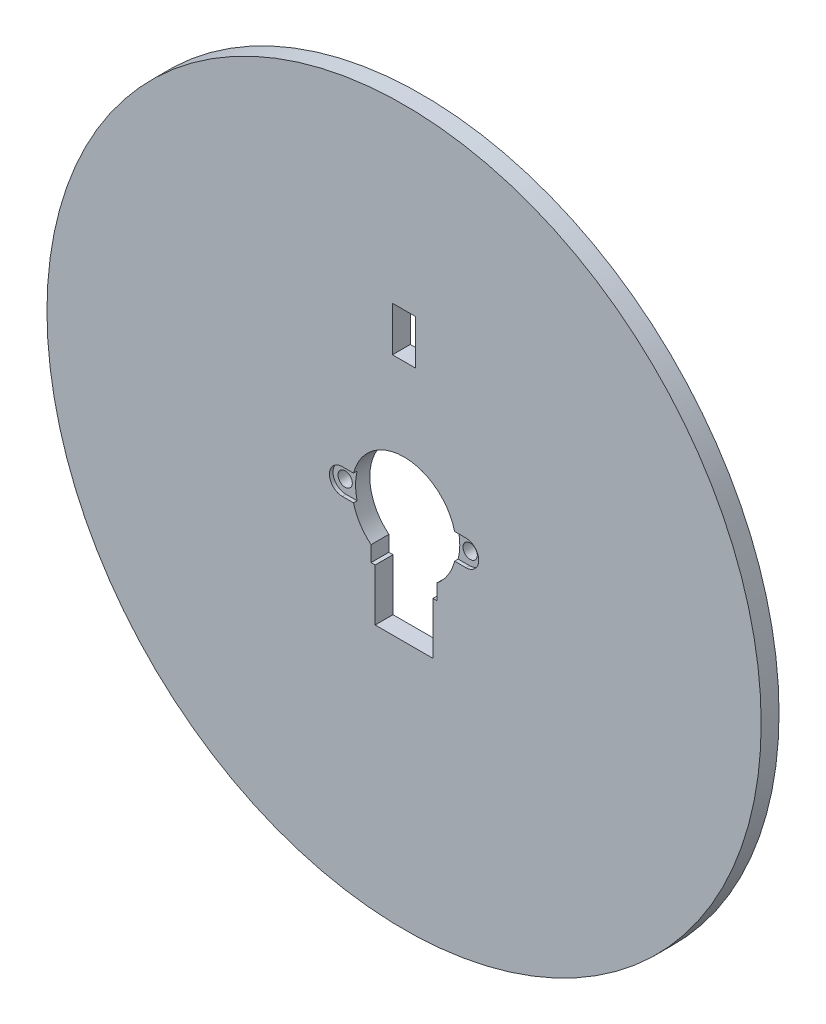
SolidWorks part; units mm, degrees
ref_plane "Front Plane" through (0, 0, 0) normal (0, 0, 1) x (1, 0, 0)
ref_plane "Top Plane" through (0, 0, 0) normal (0, 1, 0) x (1, 0, 0)
ref_plane "Right Plane" through (0, 0, 0) normal (1, 0, 0) x (0, 0, -1)
sketch "Sketch1" plane through (0, 0, 0) normal (0, 0, 1) x (1, 0, 0)
  line L0 (-121.4648, 0) -> (89.658, 0) construction
  line L1 (0, 59.7877) -> (0, -65.1952) construction
  line L2 (-14.1492, 3.6) -> (-17.3, 3.6)
  line L3 (-14.1492, -3.6) -> (-17.3, -3.6)
  line L4 (-9.25, -11.2959) -> (-9.25, -15.647)
  line L5 (14.1492, 3.6) -> (17.3, 3.6)
  line L14 (8.1, -15.647) -> (8.1, -30.2)
  line L15 (14.1492, -3.6) -> (17.3, -3.6)
  line L16 (-8.1, -30.2) -> (8.1, -30.2)
  line L24 (9.25, -11.2959) -> (9.25, -15.647)
  line L25 (8.1, -15.647) -> (9.25, -15.647)
  line L26 (-8.1, -15.647) -> (-9.25, -15.647)
  line L27 (-8.1, -15.647) -> (-8.1, -30.2)
  line L28 (-3.25, 44) -> (3.25, 44) construction
  line L29 (-3.25, 50.25) -> (3.25, 50.25)
  line L30 (-3.25, 50.25) -> (-3.25, 37.75)
  line L31 (-3.25, 37.75) -> (3.25, 37.75)
  line L32 (3.25, 50.25) -> (3.25, 37.75)
  circle A0 centre (0, 0) radius 100
  arc A2 (9.25, -11.2959) -> (-9.25, -11.2959) centre (0, 0) ccw
  arc A3 (17.3, -3.6) -> (17.3, 3.6) centre (17.3, 0) ccw
  arc A4 (-17.3, -3.6) -> (-17.3, 3.6) centre (-17.3, 0) cw
  circle A6 centre (17.5, 0) radius 2
  circle A7 centre (-17.5, 0) radius 2
  circle A8 centre (0, 56) radius 2
  circle A9 centre (0, 32) radius 2
  point P14 (0, 0)
  point P25 (0, 0)
  point P26 (0, 0)
  point P35 (0, -30.2)
  dimension "D2" = 18.5
  dimension "D3" = 14.6
  dimension "D4" = 7.2
  dimension "D8" = 4
  dimension "D5" = 200
  dimension "D13" = 4
  dimension "D6" = 1.15
  dimension "D7" = 0.2
  dimension "D9" = 6.5
  dimension "D10" = 4.3511
  dimension "D11" = 12.5
  dimension "D12" = 44
  dimension "D14" = 30.2
  dimension "D15" = 12
  dimension "D16" = 17.5
extrude "Boss-Extrude1" add sketch "Sketch1" along normal blind 5 contours A0 L3 A4 L2 A2 L5 A3 L15 L24 L25 L14 L16 L27 L26 L4 region at (-97.1716, 0, 0)
extrude "Boss-Extrude2" add sketch "Sketch1<3>" along normal blind 4 contours A4 L3 A2 L2 A7 | L15 A3 L5 A2 A6 region at (-14.6987, 0, 0) region at (15.7246, 3.5013, 0)
sketch "Sketch1<3>" plane through (0, 0, 0) normal (0, 0, 1) x (1, 0, 0) same geometry as "Sketch1"
extrude "Boss-Extrude3" add sketch "Sketch1<4>" along normal blind 1 contours A7 | A6 region at (17.5, 0, 0) region at (-17.5, 0, 0)
sketch "Sketch1<4>" plane through (0, 0, 0) normal (0, 0, 1) x (1, 0, 0) same geometry as "Sketch1"
extrude "Boss-Extrude6" add sketch "Sketch1<6>" along normal blind 5 contours A8 | A9 region at (0, 56, 0) region at (0, 32, 0)
sketch "Sketch1<6>" plane through (0, 0, 0) normal (0, 0, 1) x (1, 0, 0) same geometry as "Sketch1"
extrude "Cut-Extrude1" cut sketch "Sketch1<7>" along normal blind 3 contours A9 | A8 region at (0, 56, 0) region at (0, 32, 0)
sketch "Sketch1<7>" plane through (0, 0, 0) normal (0, 0, 1) x (1, 0, 0) same geometry as "Sketch1"
